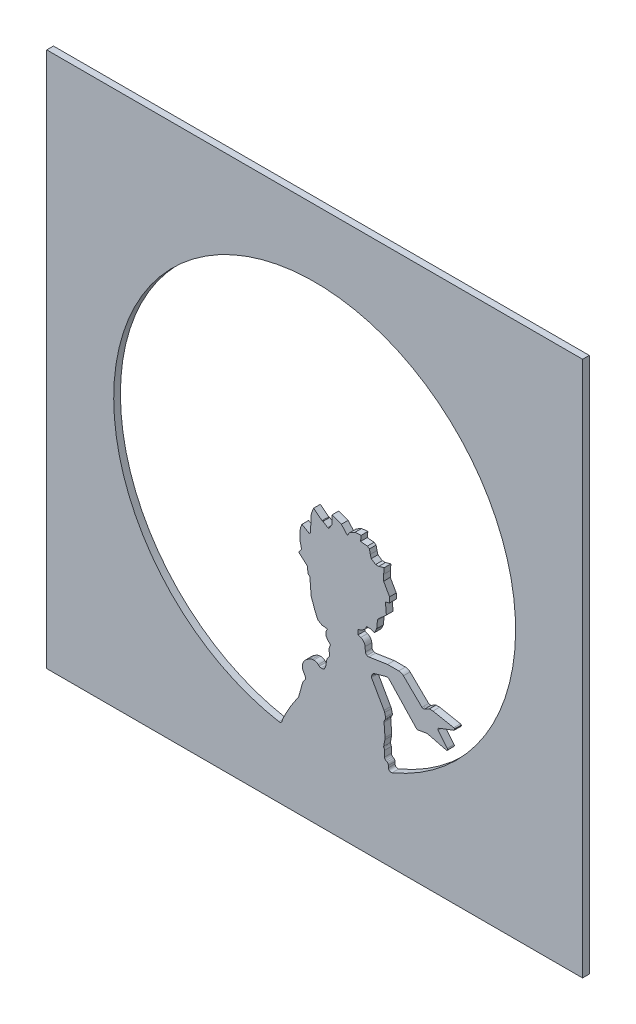
SolidWorks part; units mm, degrees
ref_plane "Plan de face" through (0, 0, 0) normal (0, 0, 1) x (1, 0, 0)
ref_plane "Plan de dessus" through (0, 0, 0) normal (0, 1, 0) x (1, 0, 0)
ref_plane "Plan de droite" through (0, 0, 0) normal (1, 0, 0) x (0, 0, -1)
sketch "Esquisse1" plane through (0, 0, 0) normal (0, 0, 1) x (1, 0, 0)
  line L1 (-200, 200) -> (200, 200)
  line L2 (-200, 200) -> (-200, -200)
  line L3 (-200, -200) -> (200, -200)
  line L4 (200, 200) -> (200, -200)
  line L5 (-200, 200) -> (200, -200) construction
  line L6 (-200, -200) -> (200, 200) construction
  circle A1 centre (0, 0) radius 150
  dimension "D1" = 400
  dimension "D2" = 300
extrude "Boss.-Extru.1" add sketch "Esquisse1" along normal blind 5
sketch "Esquisse2" plane through (0, 0, 5) normal (0, 0, 1) x (1, 0, 0)
  line L0 (55.0317, -139.5404) -> (55.0317, -133.873)
  line L1 (55.0317, -133.873) -> (52.2074, -132.2656)
  line L2 (52.2074, -132.2656) -> (52.2074, -125.6671)
  line L3 (52.2074, -125.6671) -> (51.285, -125.6671)
  line L4 (51.285, -125.6671) -> (52.5709, -119.0277)
  line L5 (52.5709, -119.0277) -> (51.7462, -108.192)
  line L6 (51.7462, -108.192) -> (53.2113, -105.6178)
  line L7 (53.2113, -105.6178) -> (52.0898, -101.6296)
  line L8 (52.0898, -101.6296) -> (42.1107, -84.0143)
  line L9 (42.1107, -84.0143) -> (43.7327, -81.1643)
  line L10 (43.7327, -81.1643) -> (54.697, -78.0811)
  line L11 (54.697, -78.0811) -> (76.4271, -101.2541)
  line L12 (76.4271, -101.2541) -> (82.8585, -100.0998)
  line L13 (82.8585, -100.0998) -> (83.9367, -99.9062)
  line L14 (83.9367, -99.9062) -> (98.6701, -103.6334)
  line L15 (98.6701, -103.6334) -> (99.6125, -102.7497)
  line L16 (99.6125, -102.7497) -> (91.3034, -92.6976)
  line L17 (91.3034, -92.6976) -> (104.813, -87.5643)
  line L18 (104.813, -87.5643) -> (104.3557, -86.3608)
  line L19 (104.3557, -86.3608) -> (88.316, -83.2543)
  line L20 (88.316, -83.2543) -> (85.4955, -83.2543)
  line L21 (85.4955, -83.2543) -> (81.9547, -85.2601)
  line L22 (81.9547, -85.2601) -> (80.3885, -85.2601)
  line L23 (80.3885, -85.2601) -> (64.8046, -70.0759)
  line L24 (64.8046, -70.0759) -> (54.4257, -70.0759)
  line L25 (54.4257, -70.0759) -> (39.7203, -72.3441)
  line L26 (39.7203, -72.3441) -> (37.9796, -71.3533)
  line L27 (37.9796, -71.3533) -> (37.4011, -63.7531)
  line L28 (37.4011, -63.7531) -> (32.494, -61.9076)
  line L29 (32.494, -61.9076) -> (32.494, -58.4862)
  line L30 (32.494, -58.4862) -> (35.5019, -57.3432)
  line L31 (35.5019, -57.3432) -> (37.9796, -55.2952)
  line L32 (37.9796, -55.2952) -> (38.6788, -53.436)
  line L33 (38.6788, -53.436) -> (42.232, -53.436)
  line L34 (42.232, -53.436) -> (44.7039, -54.3656)
  line L35 (44.7039, -54.3656) -> (46.2779, -51.169)
  line L36 (46.2779, -51.169) -> (46.9573, -44.5254)
  line L37 (46.9573, -44.5254) -> (53.5254, -38.6367)
  line L38 (53.5254, -38.6367) -> (52.8504, -30.5123)
  line L39 (52.8504, -30.5123) -> (55.9187, -29.6136)
  line L40 (55.9187, -29.6136) -> (55.9187, -25.6593)
  line L41 (55.9187, -25.6593) -> (51.4716, -17.7506)
  line L42 (51.4716, -17.7506) -> (51.4716, -13.3739)
  line L43 (51.4716, -13.3739) -> (51.9418, -8.7764)
  line L44 (51.9418, -8.7764) -> (47.8684, -9.9695)
  line L45 (47.8684, -9.9695) -> (45.4909, -9.9695)
  line L46 (45.4909, -9.9695) -> (42.232, -7.7834)
  line L47 (42.232, -7.7834) -> (41.5239, -5.3658)
  line L48 (41.5239, -5.3658) -> (40.8689, -2.193)
  line L49 (40.8689, -2.193) -> (39.3147, -1.1503)
  line L50 (39.3147, -1.1503) -> (34.2707, -0.6345)
  line L51 (34.2707, -0.6345) -> (34.6948, 3.5126)
  line L52 (34.6948, 3.5126) -> (30.0715, 3.1285)
  line L53 (30.0715, 3.1285) -> (26.1047, 0.8979)
  line L54 (26.1047, 0.8979) -> (24.4065, -1.6335)
  line L55 (24.4065, -1.6335) -> (19.9649, 3.3205)
  line L56 (19.9649, 3.3205) -> (13.0724, 5.9698)
  line L57 (13.0724, 5.9698) -> (13.0724, -0.3678)
  line L58 (13.0724, -0.3678) -> (10.6309, -4.0074)
  line L59 (10.6309, -4.0074) -> (9.7441, -4.0074)
  line L60 (9.7441, -4.0074) -> (6.2055, -1.6335)
  line L61 (6.2055, -1.6335) -> (5.5876, -1.6335)
  line L62 (5.5876, -1.6335) -> (-0.7988, 3.3205)
  line L63 (-0.7988, 3.3205) -> (-2.5215, -1.1614)
  line L64 (-2.5215, -1.1614) -> (-3.1533, -13.784)
  line L65 (-3.1533, -13.784) -> (-4.0466, -14.5849)
  line L66 (-4.0466, -14.5849) -> (-9.5151, -11.4706)
  line L67 (-9.5151, -11.4706) -> (-10.7121, -14.5849)
  line L68 (-10.7121, -14.5849) -> (-11.0877, -22.0883)
  line L69 (-11.0877, -22.0883) -> (-9.7371, -27.6364)
  line L70 (-9.7371, -27.6364) -> (-11.6194, -30.063)
  line L71 (-11.6194, -30.063) -> (-11.6194, -30.8765)
  line L72 (-11.6194, -30.8765) -> (-5.3841, -36.4468)
  line L73 (-5.3841, -36.4468) -> (-5.0014, -41.0523)
  line L74 (-5.0014, -41.0523) -> (-3.6, -42.3043)
  line L75 (-3.6, -42.3043) -> (-3.1533, -47.6798)
  line L76 (-3.1533, -47.6798) -> (-2.5978, -54.3656)
  line L77 (-2.5978, -54.3656) -> (0, -61.9076)
  line L78 (0, -61.9076) -> (2.3944, -67.3567)
  line L79 (2.3944, -67.3567) -> (5.5876, -69.1752)
  line L80 (5.5876, -69.1752) -> (9.7441, -69.6003)
  line L81 (9.7441, -69.6003) -> (8.3061, -71.7438)
  line L82 (8.3061, -71.7438) -> (8.3061, -74.1709)
  line L83 (8.3061, -74.1709) -> (9.7441, -76.7281)
  line L84 (9.7441, -76.7281) -> (11.8516, -78.6109)
  line L85 (11.8516, -78.6109) -> (10.8702, -81.1643)
  line L86 (10.8702, -81.1643) -> (10.8702, -83.876)
  line L87 (10.8702, -83.876) -> (11.3609, -85.8919)
  line L88 (11.3609, -85.8919) -> (9.1349, -89.2101)
  line L89 (9.1349, -89.2101) -> (8.1666, -94.8625)
  line L90 (8.1666, -94.8625) -> (6.8546, -97.1662)
  line L91 (6.8546, -97.1662) -> (3.991, -97.1662)
  line L92 (3.991, -97.1662) -> (1.2995, -94.7618)
  line L93 (1.2995, -94.7618) -> (-1.0646, -94.7618)
  line L94 (-1.0646, -94.7618) -> (-3.1533, -95.1929)
  line L95 (-3.1533, -95.1929) -> (-6.5708, -97.4862)
  line L96 (-6.5708, -97.4862) -> (-8.6071, -100.1113)
  line L97 (-8.6071, -100.1113) -> (-9.1632, -102.1347)
  line L98 (-9.1632, -102.1347) -> (-9.1632, -104.6768)
  line L99 (-9.1632, -104.6768) -> (-6.2981, -109.7722)
  line L100 (-6.2981, -109.7722) -> (-8.8851, -113.1073)
  line L101 (-8.8851, -113.1073) -> (-10.9156, -120.4963)
  line L102 (-10.9156, -120.4963) -> (-11.9601, -124.2971)
  line L103 (-11.9601, -124.2971) -> (-17.3133, -132.2771)
  line L104 (-17.3133, -132.2771) -> (-20.9337, -138.6341)
  line L105 (-20.9337, -138.6341) -> (-24.0208, -144.9038)
  line L106 (-24.0208, -144.9038) -> (-24.8515, -147.927)
  circle A0 centre (0, 0) radius 150 construction
  arc A1 (-24.8515, -147.927) -> (55.0317, -139.5404) centre (0, 0) ccw
  point P0 (43.7327, -81.1643)
  point P113 (54.6152, -139.5404)
extrude "Boss.-Extru.2" add sketch "Esquisse2" against normal up to vertex (5 mm away) up to point (200, -200, 0)
fillet "Congé1" radius 5 16 edges at (37.4011, -63.7531, 2.5) (64.8046, -70.0759, 2.5) (52.0898, -101.6296, 2.5) (52.5709, -119.0277, 2.5) (-24.0208, -144.9038, 2.5) (-20.9337, -138.6341, 2.5) (-17.3133, -132.2771, 2.5) (-11.9601, -124.2971, 2.5) (-8.8851, -113.1073, 2.5) (1.2995, -94.7618, 2.5) (-1.0646, -94.7618, 2.5) (-3.1533, -95.1929, 2.5) (-6.5708, -97.4862, 2.5) (-8.6071, -100.1113, 2.5) (-9.1632, -102.1347, 2.5) (-9.1632, -104.6768, 2.5)
fillet "Congé2" radius 1 6 edges at (98.6701, -103.6334, 2.5) (99.6125, -102.7497, 2.5) (91.3034, -92.6976, 2.5) (104.813, -87.5643, 2.5) (104.3557, -86.3608, 2.5) (51.285, -125.6671, 2.5)
fillet "Congé3" radius 2 21 edges at (6.8546, -97.1662, 2.5) (3.991, -97.1662, 2.5) (-6.2981, -109.7722, 2.5) (-24.8515, -147.927, 2.5) (55.0317, -139.5404, 2.5) (52.2074, -132.2656, 2.5) (55.0317, -133.873, 2.5) (52.2074, -125.6671, 2.5) (51.7462, -108.192, 2.5) (53.2113, -105.6178, 2.5) (8.1666, -94.8625, 2.5) (11.3609, -85.8919, 2.5) (9.1349, -89.2101, 2.5) (10.8702, -81.1643, 2.5) (10.8702, -83.876, 2.5) (46.9573, -44.5254, 2.5) (37.9796, -71.3533, 2.5) (39.7203, -72.3441, 2.5) (83.9367, -99.9062, 2.5) (76.4271, -101.2541, 2.5) (54.697, -78.0811, 2.5)
fillet "Congé4" radius 0.5 2 edges at (6.2055, -1.6335, 2.5) (5.5876, -1.6335, 2.5)
fillet "Congé5" radius 1 3 edges at (85.4955, -83.2543, 2.5) (81.9547, -85.2601, 2.5) (80.3885, -85.2601, 2.5)
fillet "Congé6" radius 1 2 edges at (43.7327, -81.1643, 2.5) (42.1107, -84.0143, 2.5)
sketch "Esquisse3" plane through (0, 0, 5) normal (0, 0, 1) x (1, 0, 0)
  line L0 (-0.1041, -49.9222) -> (0, -45.895)
  line L1 (10.8203, -50.8919) -> (12.3006, -49.6026)
  line L2 (11.4729, -46.6263) -> (10.6293, -46.6263)
  arc A0 (-0.1041, -49.9222) -> (0, -45.895) centre (0.1923, -47.9149) cw
  arc A1 (10.6293, -46.6263) -> (10.8203, -50.8919) centre (11.1879, -48.7383) ccw
  arc A2 (11.4729, -46.6263) -> (12.3006, -49.6026) centre (13.7995, -47.5826) ccw
sketch "Esquisse4" plane through (0, 0, 5) normal (0, 0, 1) x (1, 0, 0)
  circle A0 centre (-0.4461, -48.0671) radius 1.5
  circle A1 centre (10.5907, -48.6584) radius 1.75
  dimension "D1" = 3
  dimension "D2" = 3.5
